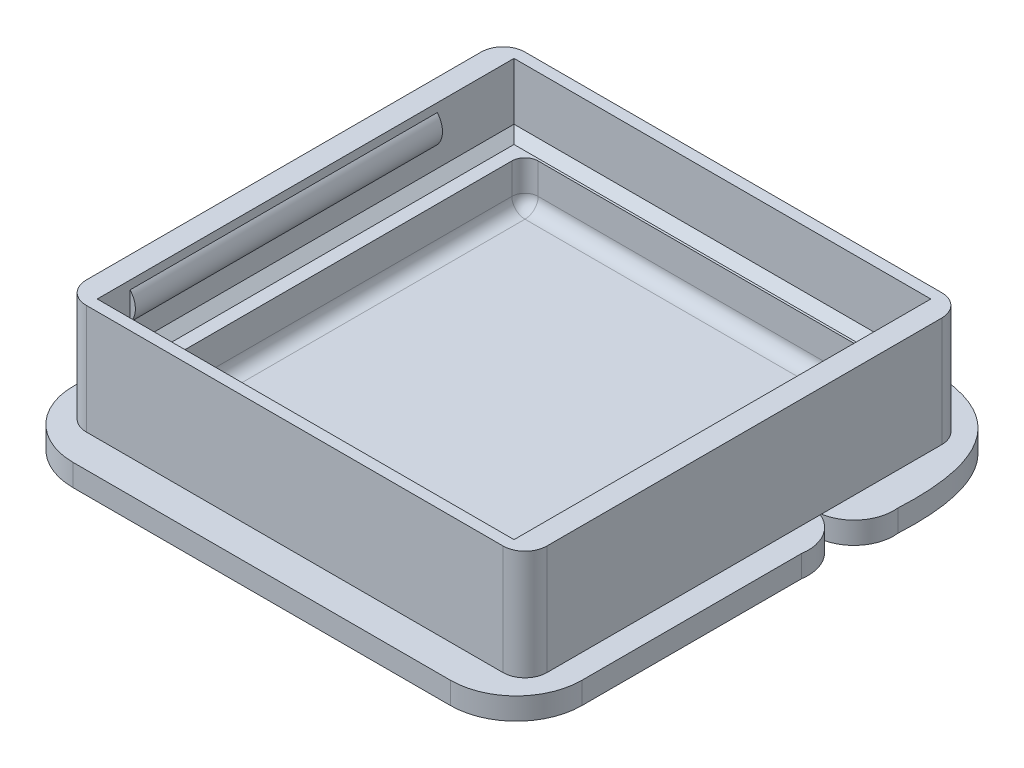
SolidWorks part; units mm, degrees
material "Teak"
ref_plane "Front Plane" through (0, 0, 0) normal (0, 0, 1) x (1, 0, 0)
ref_plane "Top Plane" through (0, 0, 0) normal (0, 1, 0) x (1, 0, 0)
ref_plane "Right Plane" through (0, 0, 0) normal (1, 0, 0) x (0, 0, -1)
sketch "Sketch2" plane through (0, 0, 0) normal (0, 1, 0) x (1, 0, 0)
  line L0 (-66.04, 22.225) -> (66.04, 22.225)
  line L1 (63.5, -66.675) -> (-63.5, -66.675)
  line L2 (63.5, -66.675) -> (63.5, 66.675)
  line L3 (63.5, 66.675) -> (-63.5, 66.675)
  line L4 (-63.5, -66.675) -> (-63.5, 66.675)
  line L5 (63.5, -66.675) -> (-63.5, 66.675) construction
  line L6 (63.5, 66.675) -> (-63.5, -66.675) construction
  line L7 (-73.66, 9.525) -> (-73.66, -53.975)
  line L8 (-54.61, -73.025) -> (54.61, -73.025)
  line L9 (73.66, -53.975) -> (73.66, 9.525)
  line L10 (-73.66, 9.525) -> (-73.66, 13.1711)
  arc A0 (-73.66, 9.525) -> (-66.04, 22.225) centre (-62.3051, 11.348) cw
  arc A1 (73.66, 9.525) -> (66.04, 22.225) centre (62.3051, 11.348) ccw
  arc A2 (-66.04, 22.225) -> (-76.2, 34.925) centre (-64.77, 33.655) cw
  arc A3 (66.04, 22.225) -> (76.2, 34.925) centre (64.77, 33.655) ccw
  arc A4 (-54.2615, 73.3341) -> (54.2615, 73.3341) centre (0, -178.2209) cw
  arc A5 (73.66, -53.975) -> (54.61, -73.025) centre (54.61, -53.975) cw
  arc A6 (-73.66, -53.975) -> (-54.61, -73.025) centre (-54.61, -53.975) ccw
  spline S0 degree 2 poles (-54.2615, 73.3341) (-78.0337, 68.7721) (-76.2, 34.925) knots 0 0 0 1 1 1
  spline S1 degree 2 poles (54.2615, 73.3341) (78.0337, 68.7721) (76.2, 34.925) knots 0 0 0 1 1 1
  point P0 (0, 0)
  dimension "D11" = 11.5003
  dimension "D12" = 11.5003
  dimension "D14" = 11.5003
  dimension "D15" = 11.5003
  dimension "D17" = 19.05
  dimension "D1" = 133.35
  dimension "D2" = 127
  dimension "D3" = 44.45
  dimension "D4" = 2.54
  dimension "D5" = 2.54
  dimension "D6" = 10.16
  dimension "D7" = 10.16
  dimension "D8" = 6.35
  dimension "D9" = 12.7
  dimension "D10" = 12.7
  dimension "D13" = 12.7
extrude "Boss-Extrude1" add sketch "Sketch2" along normal blind 6.35 contours L7 A6 L8 A5 L9 A1 L0 L2 L1 L4 A0 L10 | L4 L1 L2 L0 | L4 L0 L2 | A2 L0 L4 L10 | S1 A4 S0 L10 L4 L3 L2 | L4 L2 L3 | L0 A3 L2 region at (-72.4781, 0, -27.4885) region at (-64.77, 0, -20.4695) region at (0, 0, -44.45) region at (0, 0, 22.225)
sketch "Sketch3" plane through (0, 6.35, 0) normal (0, 1, 0) x (1, 0, 0)
  line L1 (-53.975, 57.15) -> (53.975, 57.15)
  line L2 (-53.975, 57.15) -> (-53.975, -57.15)
  line L3 (-53.975, -57.15) -> (53.975, -57.15)
  line L4 (53.975, 57.15) -> (53.975, -57.15)
  line L5 (-53.975, 57.15) -> (53.975, -57.15) construction
  line L6 (-53.975, -57.15) -> (53.975, 57.15) construction
  line L8 (-66.675, 63.5) -> (66.675, 63.5)
  line L9 (-66.675, 63.5) -> (-66.675, -63.5)
  line L10 (-66.675, -63.5) -> (66.675, -63.5)
  line L11 (66.675, 63.5) -> (66.675, -63.5)
  line L12 (-66.675, 63.5) -> (66.675, -63.5) construction
  line L13 (-66.675, -63.5) -> (66.675, 63.5) construction
  point P0 (0, 0)
  point P10 (0, 0)
  dimension "D1" = 107.95
  dimension "D2" = 114.3
  dimension "D3" = 12.7
  dimension "D4" = 6.35
extrude "Boss-Extrude2" add sketch "Sketch3" along normal blind 12.7
sketch "Sketch4" plane through (0, 19.05, 0) normal (0, 1, 0) x (1, 0, 0)
  line L0 (53.975, -57.15) -> (53.975, 57.15) construction
  line L1 (-66.675, 63.5) -> (66.675, 63.5)
  line L2 (-66.675, 63.5) -> (-66.675, -63.5)
  line L3 (-66.675, -63.5) -> (66.675, -63.5)
  line L4 (66.675, 63.5) -> (66.675, -63.5)
  line L5 (-66.675, 63.5) -> (66.675, -63.5) construction
  line L6 (-66.675, -63.5) -> (66.675, 63.5) construction
  line L7 (-60.325, 60.325) -> (60.325, 60.325)
  line L8 (-60.325, 60.325) -> (-60.325, -60.325)
  line L9 (-60.325, -60.325) -> (60.325, -60.325)
  line L10 (60.325, 60.325) -> (60.325, -60.325)
  line L11 (-60.325, 60.325) -> (60.325, -60.325) construction
  line L12 (-60.325, -60.325) -> (60.325, 60.325) construction
  point P0 (0, 0)
  point P7 (0, 0)
  dimension "D1" = 6.35
  dimension "D2" = 3.175
extrude "Boss-Extrude3" add sketch "Sketch4" along normal blind 19.05
fillet "Fillet1" radius 6.35 4 edges at (-66.675, 22.225, -63.5) (66.675, 22.225, -63.5) (66.675, 22.225, 63.5) (-66.675, 22.225, 63.5)
fillet "Fillet2" radius 3.81 4 edges at (-53.975, 6.35, 0) (0, 6.35, 57.15) (53.975, 6.35, 0) (0, 6.35, -57.15)
sketch "Sketch5" plane through (0, 0, 0) normal (0, 0, 1) x (1, 0, 0)
  line L4 (60.325, 35.6221) -> (60.325, 27.5579)
  line L5 (-60.325, 35.6221) -> (-60.325, 27.5579)
  arc A0 (60.325, 35.6221) -> (60.325, 27.5579) centre (64.897, 31.59) ccw
  arc A1 (-60.325, 35.6221) -> (-60.325, 27.5579) centre (-64.897, 31.59) cw
  dimension "D3" = 12.192
  dimension "D5" = 4.572
extrude "Boss-Extrude4" add sketch "Sketch5" along normal blind 50.8 and the other way blind 38.1
chamfer "Chamfer1" distance 2.54 angle 45 4 edges at (0, 19.05, 60.325) (60.325, 19.05, 0) (0, 19.05, -60.325) (-60.325, 19.05, 0)
sketch "Sketch6" plane through (0, 0, 0) normal (0, -1, 0) x (1, 0, 0)
  text T0 "<b>SJKELLY</b>"
extrude "Cut-Extrude1" cut sketch "Sketch6" against normal blind 2.54
fillet "Fillet3" radius 3.81 8 edges at (-52.8591, 7.4659, -56.0341) (-52.8591, 7.4659, 56.0341) (52.8591, 7.4659, 56.0341) (52.8591, 7.4659, -56.0341) (-53.975, 14.605, -57.15) (-53.975, 14.605, 57.15) (53.975, 14.605, 57.15) (53.975, 14.605, -57.15)
